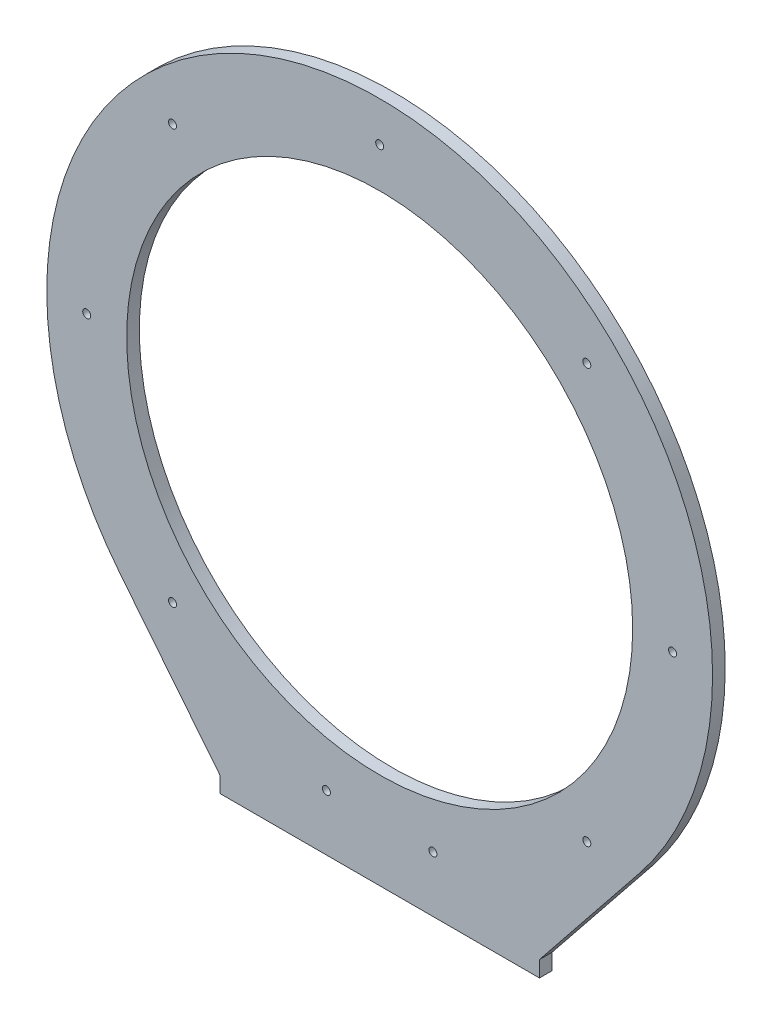
SolidWorks part; units mm, degrees
note: '?' marks a value the reader was unsure of.
ref_plane "Front Plane" through (0, 0, 0) normal (0, 0, 1) x (1, 0, 0)
ref_plane "Top Plane" through (0, 0, 0) normal (0, 1, 0) x (1, 0, 0)
ref_plane "Right Plane" through (0, 0, 0) normal (1, 0, 0) x (0, 0, -1)
sketch "Sketch1" plane through (0, 0, 0) normal (0, 0, 1) x (1, 0, 0)
  line L0 (0, -95) -> (0, -125) construction
  line L1 (-95, 0) -> (95, 0) construction
  line L2 (-67.1751, -67.1751) -> (67.1751, 67.1751) construction
  line L3 (-67.1751, 67.1751) -> (67.1751, -67.1751) construction
  line L4 (67.1751, -67.1751) -> (88.3883, -88.3883) construction
  line L5 (67.1751, 67.1751) -> (88.3883, 88.3883) construction
  line L6 (0, 95) -> (0, -95) construction
  line L7 (95, 0) -> (125, 0) construction
  line L23 (-60, -125) -> (-97.5293, -78.186)
  line L30 (-60, -125) -> (-60, -131)
  line L31 (-60, -131) -> (60, -131)
  line L32 (60, -125) -> (60, -131)
  line L33 (-60, -125) -> (60, -131) construction
  line L34 (-60, -131) -> (60, -125) construction
  line L35 (60, -125) -> (97.5293, -78.186)
  circle A3 centre (77.7817, -77.7817) radius 1.5
  circle A5 centre (77.7817, 77.7817) radius 1.5
  circle A6 centre (-77.7817, -77.7817) radius 1.5
  circle A7 centre (0, 110) radius 1.5
  circle A8 centre (-77.7817, 77.7817) radius 1.5
  circle A9 centre (110, 0) radius 1.5
  circle A10 centre (-110, 0) radius 1.5
  arc A22 (88.3883, -88.3883) -> (-97.5293, -78.186) centre (0, 0) ccw
  circle A23 centre (0, 0) radius 95
  circle A24 centre (-20, -110) radius 1.5
  circle A25 centre (20, -110) radius 1.5
  point P1 (0, -128)
  point P3 (0, -128)
  point P11 (0, 0)
  point P14 (0, 0)
  point P31 (0, -128)
  point P47 (0, -125)
  point P55 (-67.1751, -105.4158)
  dimension "D1" = 15
  dimension "D2" = 15
  dimension "D3" = 15
  dimension "D5" = 15
  dimension "D6" = 3
extrude "Boss-Extrude1" add sketch "Sketch1" along normal blind 4.75
convert to sheet metal "Convert-Solid1" [suppressed] bend radius? 10 thickness? 4.75
sketch "Bend-Lines1" [suppressed] plane through (0, 0, 0) normal (0, 1, 0) x (1, 0, 0)
sketch "Bounding-Box1" [suppressed] plane through (0, 0, 0) normal (0, 1, 0) x (1, 0, 0)
sheet metal parameters "Sheet-Metal2" thickness 4.75 parameters "D1"=10
flat pattern "Flat-Pattern2" [suppressed]
sketch "Bend-Lines2" plane through (0, 0, 0) normal (0, 1, 0) x (1, 0, 0)
sketch3d "Bounding-Box2" [suppressed]
  line L0 (125, 125, 0) -> (125, -131, 0) construction
  line L1 (-125, 125, 0) -> (-125, -131, 0) construction
  line L2 (125, 125, 0) -> (-125, 125, 0) construction
  line L3 (125, -131, 0) -> (-125, -131, 0) construction
